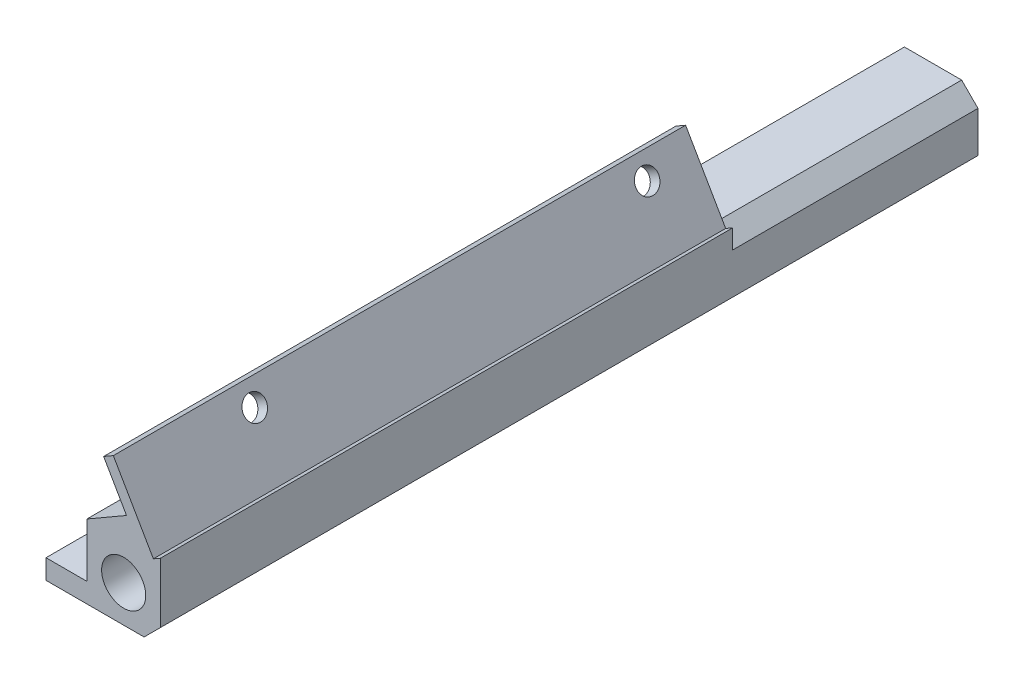
SolidWorks part; units mm, degrees
ref_plane "Front Plane" through (0, 0, 0) normal (0, 0, 1) x (1, 0, 0)
ref_plane "Top Plane" through (0, 0, 0) normal (0, 1, 0) x (1, 0, 0)
ref_plane "Right Plane" through (0, 0, 0) normal (1, 0, 0) x (0, 0, -1)
sketch "Sketch1" plane through (0, 0, 0) normal (0, 1, 0) x (1, 0, 0)
  line L1 (0, 0) -> (77.47, 0)
  line L2 (0, 0) -> (0, 127)
  line L3 (0, 127) -> (77.47, 127)
  line L4 (77.47, 0) -> (77.47, 127)
  dimension "D1" = 77.47
  dimension "D2" = 127
extrude "Boss-Extrude1" add sketch "Sketch1" along normal blind 11.43
sketch "Sketch2" plane through (0, 0, 0) normal (0, 0, 1) x (1, 0, 0)
  line L0 (5.715, 5.715) -> (71.755, 5.715) construction
  line L1 (38.735, 11.43) -> (38.735, 0) construction
  line L2 (0, 11.43) -> (77.47, 11.43) construction
  line L3 (0, 0) -> (77.47, 0) construction
  circle A0 centre (5.715, 5.715) radius 3.429
  circle A1 centre (71.755, 5.715) radius 3.429
  point P10 (38.735, 5.715)
  dimension "D1" = 6.858
  dimension "D2" = 66.04
extrude "Cut-Extrude1" cut sketch "Sketch2" against normal through all
sketch "Sketch3" plane through (0, 11.43, 0) normal (0, 1, 0) x (1, 0, 0)
  line L0 (11.43, 127) -> (11.43, 88.9)
  line L1 (77.47, 127) -> (0, 127) construction
  line L2 (11.43, 127) -> (66.04, 127)
  line L3 (66.04, 127) -> (66.04, 88.9)
  line L4 (53.34, 76.2) -> (24.13, 76.2)
  line L5 (0, 127) -> (0, 0) construction
  arc A0 (66.04, 88.9) -> (53.34, 76.2) centre (53.34, 88.9) cw
  arc A1 (24.13, 76.2) -> (11.43, 88.9) centre (24.13, 88.9) cw
  point P10 (38.735, 127)
  dimension "D1" = 12.7
  dimension "D2" = 11.43
  dimension "D3" = 50.8
extrude "Cut-Extrude2" cut sketch "Sketch3" against normal through all
sketch "Sketch4" plane through (0, 0, -127) normal (0, 0, -1) x (-1, 0, 0)
  line L0 (-11.43, 0) -> (-11.43, 11.43) construction
  line L1 (-66.04, 11.43) -> (-11.43, 11.43)
  line L2 (-66.04, 11.43) -> (-66.04, 5.08)
  line L3 (-66.04, 5.08) -> (-11.43, 5.08)
  line L4 (-11.43, 11.43) -> (-11.43, 5.08)
  line L5 (-11.43, 0) -> (0, 0) construction
  dimension "D1" = 5.08
extrude "Cut-Extrude3" cut sketch "Sketch4" against normal through all
chamfer "Chamfer1" distance 2.54 angle 45 4 edges at (0, 0, -63.5) (0, 11.43, -63.5) (77.47, 0, -63.5) (77.47, 11.43, -63.5)
sketch "Sketch5" plane through (0, 11.43, 0) normal (0, 1, 0) x (1, 0, 0)
  line L0 (66.04, 76.2) -> (0, 76.2)
  line L1 (66.04, 0) -> (66.04, 88.9) construction
  line L2 (0, 0) -> (0, 127) construction
  line L3 (0, 76.2) -> (0, 127)
  line L4 (0, 127) -> (66.04, 127)
  line L5 (66.04, 127) -> (66.04, 76.2)
  line L6 (24.13, 76.2) -> (53.34, 76.2) construction
extrude "Cut-Extrude4" cut sketch "Sketch5" against normal through all
sketch "Sketch6" plane through (0, 11.43, 0) normal (0, 1, 0) x (1, 0, 0)
  line L0 (53.34, 76.2) -> (53.34, 0)
  line L1 (11.43, 76.2) -> (66.04, 76.2) construction
  line L2 (66.04, 0) -> (11.43, 0) construction
  line L3 (53.34, 0) -> (0, 0)
  line L4 (0, 0) -> (0, 76.2)
  line L5 (0, 76.2) -> (53.34, 76.2)
  line L6 (66.04, 0) -> (66.04, 127) construction
  dimension "D1" = 12.7
extrude "Cut-Extrude5" cut sketch "Sketch6" against normal through all
sketch "Sketch7" plane through (0, 5.08, 0) normal (0, 1, 0) x (1, 0, 0)
  line L0 (53.34, 76.2) -> (66.04, 76.2) construction
  line L1 (66.04, 0) -> (66.04, 76.2) construction
  circle A0 centre (62.23, 68.58) radius 1.778
  circle A4 centre (62.23, 7.62) radius 1.778
  dimension "D1" = 3.556
  dimension "D2" = 7.62
  dimension "D3" = 68.58
  dimension "D4" = 3.81
extrude "Hole Cuts 1" cut sketch "Sketch7" against normal through all
sketch "Sketch8" plane through (0, 0, 0) normal (0, 0, 1) x (1, 0, 0)
  line L0 (77.47, 11.8699) -> (77.47, 7.0306)
  line L1 (77.47, 11.8699) -> (71.882, 21.5486)
  line L2 (71.882, 21.5486) -> (68.6183, 19.6643)
  line L3 (68.6183, 19.6643) -> (71.5393, 14.605)
  line L4 (71.5393, 14.605) -> (66.04, 11.43)
  line L5 (77.47, 11.43) -> (68.58, 11.43) construction
  line L6 (66.04, 11.43) -> (74.93, 11.43) construction
  line L7 (66.04, 11.43) -> (74.93, 11.43)
  line L8 (74.93, 11.43) -> (77.47, 7.0306)
  line L9 (77.47, 8.89) -> (77.47, 2.54) construction
  dimension "D2" = 11.176
  dimension "D3" = 6.35
  dimension "D4" = 5.842
  dimension "D6" = 60
extrude "Boss-Extrude2" add sketch "Sketch8" against normal blind 88.9
sketch "Sketch9" plane through (0, 0, 0) normal (0, 0, 1) x (1, 0, 0)
  line L0 (74.93, 0) -> (66.04, 0) construction
  line L1 (53.34, 0) -> (74.93, 0) construction
  line L3 (66.04, 0) -> (59.69, 0) construction
  line L4 (59.69, 0) -> (53.34, 0)
  line L5 (53.34, 0) -> (53.34, 5.08)
  line L6 (53.34, 5.08) -> (59.69, 5.08)
  line L7 (66.04, 5.08) -> (53.34, 5.08) construction
  line L8 (59.69, 5.08) -> (59.69, 0)
  dimension "D1" = 6.35
extrude "Cut-Extrude7" cut sketch "Sketch9" against normal up to next
sketch "Sketch10" plane through (0, 0, 0) normal (0, 0, 1) x (1, 0, 0)
  line L0 (59.69, 5.08) -> (66.04, 5.08)
  line L1 (66.04, 5.08) -> (66.04, 3.81)
  line L2 (66.04, 3.81) -> (59.69, 3.81)
  line L3 (59.69, 0) -> (59.69, 5.08) construction
  line L4 (59.69, 3.81) -> (59.69, 5.08)
  line L5 (59.69, 0) -> (74.93, 0) construction
  dimension "D1" = 3.81
extrude "Cut-Extrude8" cut sketch "Sketch10" against normal up to next
sketch "Sketch11" plane through (59.9786, 34.6287, 0) normal (-0.866, -0.5, 0) x (0, 0, 1)
  line L0 (-88.9, -23.1213) -> (0, -23.1213) construction
  line L1 (-88.9, -17.2793) -> (-88.9, -23.1213) construction
  circle A0 centre (-20.32, -19.3113) radius 1.778
  circle A1 centre (-81.28, -19.3113) radius 1.778
  dimension "D1" = 3.556
  dimension "D2" = 3.81
  dimension "D3" = 7.62
  dimension "D4" = 68.58
extrude "Hole Cuts 2" cut sketch "Sketch11" against normal up to next
sketch "Sketch12" plane through (63.2423, 36.513, 0) normal (0.866, 0.5, 0) x (0, 0, -1)
  line L1 (88.9, -17.2793) -> (0, -17.2793)
  line L2 (88.9, -17.2793) -> (88.9, -28.4553)
  line L3 (88.9, -28.4553) -> (0, -28.4553)
  line L4 (0, -17.2793) -> (0, -28.4553)
extrude "Cut-Extrude10" cut sketch "Sketch12" against normal blind 1.27
sketch "Sketch13" plane through (59.9786, 34.6287, 0) normal (-0.866, -0.5, 0) x (0, 0, 1)
  line L1 (-88.9, -17.2793) -> (0, -17.2793)
  line L2 (-88.9, -17.2793) -> (-88.9, -23.1213)
  line L3 (-88.9, -23.1213) -> (0, -23.1213)
  line L4 (0, -17.2793) -> (0, -23.1213)
extrude "Cut-Extrude11" cut sketch "Sketch13" against normal blind 0.762
sketch "Sketch14" plane through (0, 3.81, 0) normal (0, 1, 0) x (1, 0, 0)
  line L1 (59.69, 76.2) -> (66.04, 76.2)
  line L2 (59.69, 76.2) -> (59.69, 0)
  line L3 (59.69, 0) -> (66.04, 0)
  line L4 (66.04, 76.2) -> (66.04, 0)
extrude "Cut-Extrude12" cut sketch "Sketch14" against normal blind 0.762
sketch "Sketch15" plane through (8.6397, -14.9643, 0) normal (-0.5, 0.866, 0) x (0.866, 0.5, 0)
  line L1 (71.756, 0) -> (70.0193, 0)
  line L2 (71.756, 0) -> (71.756, 88.9)
  line L3 (71.756, 88.9) -> (70.0193, 88.9)
  line L4 (70.0193, 0) -> (70.0193, 88.9)
extrude "Boss-Extrude3" add sketch "Sketch15" along normal blind 1.27
